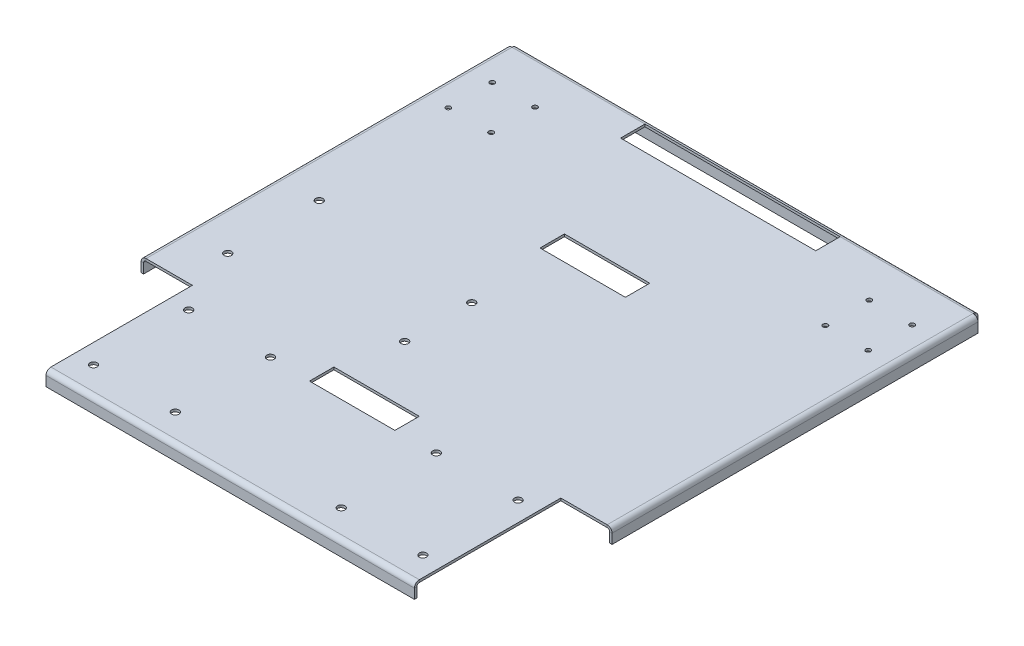
SolidWorks part; units mm, degrees
note: The reader was unsure of these and kept them because the rebuilt part matched: flange length of "Edge-Flange1", "Edge-Flange2", "Edge-Flange3", "Edge-Flange4".
ref_plane "Front Plane" through (0, 0, 0) normal (0, 0, 1) x (1, 0, 0)
ref_plane "Top Plane" through (0, 0, 0) normal (0, 1, 0) x (1, 0, 0)
ref_plane "Right Plane" through (0, 0, 0) normal (1, 0, 0) x (0, 0, -1)
sketch "Sketch1" plane through (0, 0, 0) normal (0, 1, 0) x (1, 0, 0)
  line L1 (-94.5, 104) -> (94.5, 104)
  line L2 (-94.5, 104) -> (-94.5, -104)
  line L3 (-94.5, -104) -> (94.5, -104)
  line L4 (94.5, 104) -> (94.5, -104)
  line L5 (-94.5, 104) -> (94.5, -104) construction
  line L6 (-94.5, -104) -> (94.5, 104) construction
  point P0 (0, 0)
  dimension "D1" = 208
  dimension "D2" = 189
sheet metal parameters "Sheet-Metal1" thickness 1 parameters "D1"=1
base flange "Base-Flange1" sketch "Sketch1" thickness 1 reverse thickness direction no parameters "D1"=1
edge flange "Edge-Flange1" sketch "Sketch6" flange angle 90 flange length 5 flange position bend outside bend radius 1 thickness 1 relief rectangular parameters "D6"=10
sketch "Sketch6" plane through (0, -1, 104) normal (0, 0, 1) x (-1, 0, 0)
  line L2 (-94.5, 0) -> (-94.5, 5)
  line L3 (-94.5, 5) -> (94.5, 5)
  line L4 (94.5, 5) -> (94.5, 0)
  line L5 (94.5, 0) -> (-94.5, 0) construction
  line L6 (94.5, 0) -> (-94.5, 0)
bend "EdgeBend1" bend radius 1 bend angle 90 parameters "D5"=1
edge flange "Edge-Flange2" sketch "Sketch9" flange angle 90 flange length 5 flange position bend outside bend radius 1 thickness 1 relief rectangular parameters "D6"=10
sketch "Sketch9" plane through (94.5, -1, 0) normal (1, 0, 0) x (0, 0, 1)
  line L0 (104, 0) -> (-104, 0) construction
  line L1 (104, 0) -> (-104, 0)
  line L2 (-104, 0) -> (-104, 5)
  line L3 (-104, 5) -> (104, 5)
  line L4 (104, 5) -> (104, 0)
bend "EdgeBend2" bend radius 1 bend angle 90 parameters "D5"=2
edge flange "Edge-Flange3" sketch "Sketch12" flange angle 90 flange length 5 flange position bend outside bend radius 1 thickness 1 relief rectangular parameters "D6"=10
sketch "Sketch12" plane through (0, -1, -104) normal (0, 0, -1) x (1, 0, 0)
  line L0 (94.5, 0) -> (-94.5, 0) construction
  line L1 (94.5, 0) -> (-94.5, 0)
  line L2 (-94.5, 0) -> (-94.5, 5)
  line L3 (-94.5, 5) -> (94.5, 5)
  line L4 (94.5, 5) -> (94.5, 0)
bend "EdgeBend3" bend radius 1 bend angle 90 parameters "D5"=3
edge flange "Edge-Flange4" sketch "Sketch15" flange angle 90 flange length 5 flange position bend outside bend radius 1 thickness 1 relief rectangular parameters "D6"=10
sketch "Sketch15" plane through (-94.5, -1, 0) normal (-1, 0, 0) x (0, 0, -1)
  line L0 (104, 0) -> (-104, 0) construction
  line L1 (104, 0) -> (-104, 0)
  line L2 (-104, 0) -> (-104, 5)
  line L3 (-104, 5) -> (104, 5)
  line L4 (104, 5) -> (104, 0)
bend "EdgeBend4" bend radius 1 bend angle 90 parameters "D5"=4
sketch "Sketch16" plane through (0, 0, 0) normal (0, 1, 0) x (1, 0, 0)
  line L0 (-24.2164, 108.0191) -> (-24.2164, 82.9902)
  line L1 (-24.2164, 82.9902) -> (-19.6657, 82.9902)
  line L2 (-19.6657, 82.9902) -> (-19.6657, 92.5972)
  line L3 (-19.6657, 92.5972) -> (-11.6222, 92.5972)
  line L4 (-11.6222, 92.5972) -> (-11.6222, 97.4008)
  line L5 (-11.6222, 97.4008) -> (-19.6657, 97.4008)
  line L6 (-19.6657, 97.4008) -> (-19.6657, 104.2268)
  line L7 (-19.6657, 104.2268) -> (-11.5755, 104.2268)
  line L8 (-11.5755, 104.2268) -> (-11.5755, 108.0191)
  line L9 (-11.5755, 108.0191) -> (-24.2164, 108.0191)
  line L10 (-24.2164, -84.4164) -> (-24.2164, -107.2854)
  line L11 (-24.2164, -107.2854) -> (-19.6657, -107.2854)
  line L12 (-21.752, -87.184) -> (-21.752, -92.5358)
  line L13 (-24.2164, -84.4164) -> (-19.6657, -84.4164)
  line L14 (-21.752, -92.5358) -> (-19.6657, -92.5358)
  line L15 (-21.752, -87.184) -> (-19.6657, -87.184)
  line L16 (-21.752, -98.2645) -> (-21.752, -105.2746)
  line L17 (-21.752, -98.2645) -> (-19.6657, -98.2645)
  line L18 (-21.752, -105.2746) -> (-19.6657, -105.2746)
  arc A0 (-19.6657, -84.4164) -> (-19.6657, -95.8509) centre (-19.6657, -90.1336) cw
  arc A1 (-19.6657, -95.8509) -> (-19.6657, -107.2854) centre (-19.6657, -101.5682) cw
  arc A2 (-19.6657, -87.184) -> (-19.6657, -92.5358) centre (-19.6657, -89.8599) cw
  arc A3 (-19.6657, -98.2645) -> (-19.6657, -105.2746) centre (-19.6657, -101.7695) cw
sketch "Sketch17" plane through (0, 0, 0) normal (0, 1, 0) x (1, 0, 0)
  line L0 (96.5, -104) -> (96.5, 104) construction
  line L1 (96.5, -106) -> (75.5, -106)
  line L2 (96.5, -106) -> (96.5, -46)
  line L3 (96.5, -46) -> (75.5, -46)
  line L4 (75.5, -106) -> (75.5, -46)
  line L5 (-94.5, -106) -> (94.5, -106) construction
  line L6 (0, -137.1955) -> (0, 137.1164) construction
  line L7 (-75.5, -106) -> (-75.5, -46)
  line L8 (-96.5, -46) -> (-75.5, -46)
  line L9 (-96.5, -106) -> (-96.5, -46)
  line L10 (-96.5, -106) -> (-75.5, -106)
  dimension "D1" = 0
  dimension "D2" = 60
  dimension "D3" = 21
extrude "Cut-Extrude1" cut sketch "Sketch17" against normal through all normal cut yes
sketch "Sketch18" plane through (0, 0, 0) normal (0, 1, 0) x (1, 0, 0)
  line L0 (0, -59.5649) -> (0, 146.0466) construction
  line L1 (94.5, 104) -> (-94.5, 104) construction
  line L2 (-40, 104) -> (40, 104)
  line L3 (-40, 104) -> (-40, 94)
  line L4 (-40, 94) -> (40, 94)
  line L5 (40, 104) -> (40, 94)
  line L6 (-40, 104) -> (40, 94) construction
  line L7 (-40, 94) -> (40, 104) construction
  point P3 (0, 99)
  dimension "D1" = 10
  dimension "D2" = 0
  dimension "D3" = 80
extrude "Cut-Extrude2" cut sketch "Sketch18" against normal blind 10 normal cut yes
sketch "Sketch20" plane through (0, 0, 0) normal (0, 1, 0) x (1, 0, 0)
  line L0 (-85, -46) -> (85, -46) construction
  line L1 (-75.5, -46) -> (-94.5, -46) construction
  line L2 (94.5, -46) -> (75.5, -46) construction
  line L3 (-94.5, 104) -> (-94.5, -46) construction
  line L4 (-94.5, -8.6649) -> (18.6476, -8.6649) construction
  circle A0 centre (-79.5844, -27.4149) radius 1.5
  circle A1 centre (-12.0844, -22.4149) radius 1.5
  circle A2 centre (-12.0844, 5.0851) radius 1.5
  circle A3 centre (-79.5844, 10.0851) radius 1.5
  dimension "D2" = 18.5851
  dimension "D3" = 3
  dimension "D4" = 3
  dimension "D5" = 67.5
  dimension "D6" = 5
  dimension "D1" = 14.9156
  dimension "D7" = 18.75
extrude "Cut-Extrude3" cut sketch "Sketch20" against normal blind 10 normal cut yes
sketch "Sketch21" plane through (0, 0, 0) normal (0, 1, 0) x (1, 0, 0)
  line L0 (-93.9966, 33.4732) -> (94.5, 33.4732) construction
  line L1 (94.5, -46) -> (94.5, 104) construction
  line L2 (77.2791, 93.0875) -> (77.2791, 62.1867) construction
  line L7 (63.9469, 78.4496) -> (91.7327, 78.4496) construction
  line L8 (0, 109.5327) -> (0, -141.8529) construction
  circle A0 centre (68.5, 87.4496) radius 1
  circle A1 centre (86.0583, 87.4496) radius 1
  circle A2 centre (68.5, 69.4496) radius 1
  circle A3 centre (86.0583, 69.4496) radius 1
  circle A4 centre (-86.0583, 87.4496) radius 1
  circle A5 centre (-86.0583, 69.4496) radius 1
  circle A6 centre (-68.5, 69.4496) radius 1
  circle A7 centre (-68.5, 87.4496) radius 1
  dimension "D6" = 2
extrude "Cut-Extrude4" cut sketch "Sketch21" against normal blind 10 normal cut yes
sketch "Sketch22" plane through (0, 0, 0) normal (0, 1, 0) x (1, 0, 0)
  line L0 (-75.5, -75) -> (102.8979, -75) construction
  line L1 (-75.5, -104) -> (-75.5, -46) construction
  line L2 (75.5, -46) -> (75.5, -104) construction
  line L9 (-80.5, -49) -> (80.5, -49) construction
  line L10 (-29, -51.5) -> (-29, -70) construction
  line L11 (29, -51.5) -> (29, -70) construction
  line L13 (0, -30.5194) -> (0, -140) construction
  line L14 (-80.5, -89) -> (80.5, -89) construction
  circle A0 centre (67.5, -55.5) radius 1.5
  circle A1 centre (34, -55.5) radius 1.5
  circle A2 centre (34, -94.5) radius 1.5
  circle A3 centre (67.5, -94.5) radius 1.5
  circle A4 centre (-67.5, -94.5) radius 1.5
  circle A5 centre (-34, -94.5) radius 1.5
  circle A8 centre (-34, -55.5) radius 1.5
  circle A9 centre (-67.5, -55.5) radius 1.5
  dimension "D4" = 33.5
  dimension "D1" = 8
  dimension "D2" = 8
  dimension "D3" = 33.5
extrude "Cut-Extrude5" cut sketch "Sketch22" against normal blind 10 normal cut yes
sketch "Sketch23" plane through (0, 0, 0) normal (0, 1, 0) x (1, 0, 0)
  line L0 (-93.9966, 33.4732) -> (94.5, 33.4732) construction
  line L1 (94.5, -46) -> (94.5, 104) construction
  line L2 (0, 94) -> (0, 48.4732) construction
  line L3 (-17.5, 38.4732) -> (17.5, 38.4732)
  line L4 (-17.5, 38.4732) -> (-17.5, 48.4732)
  line L5 (-17.5, 48.4732) -> (17.5, 48.4732)
  line L6 (17.5, 38.4732) -> (17.5, 48.4732)
  line L7 (-40, 94) -> (40, 94) construction
  line L8 (-92.7332, -3.7634) -> (92.74, -3.7634) construction
  line L9 (-92.7332, -38.7634) -> (-92.7332, 31.2366) construction
  line L10 (92.74, 31.2366) -> (92.74, -38.7634) construction
  line L11 (-17.5, -46) -> (-17.5, -56)
  line L12 (-17.5, -46) -> (17.5, -46)
  line L13 (17.5, -46) -> (17.5, -56)
  line L14 (-17.5, -56) -> (17.5, -56)
  dimension "D1" = 5
  dimension "D2" = 35
  dimension "D3" = 10
extrude "Cut-Extrude6" cut sketch "Sketch23" against normal blind 10 normal cut yes
flat pattern "Flat-Pattern1" [suppressed]
sketch "Bend-Lines1" plane through (0, 0, 0) normal (0, 1, 0) x (1, 0, 0)
  line L0 (-95.6781, 99) -> (-95.6781, -41) construction
  line L1 (94.5, 100.1781) -> (-94.5, 100.1781) construction
  line L2 (95.6781, -41) -> (95.6781, 99) construction
  line L3 (-75.5, -100.1781) -> (75.5, -100.1781) construction
  line L4 (-95.6781, 99) -> (-95.6781, -41) construction
  line L5 (94.5, 100.1781) -> (-94.5, 100.1781) construction
  line L6 (95.6781, -41) -> (95.6781, 99) construction
  line L7 (-75.5, -100.1781) -> (75.5, -100.1781) construction
sketch3d "Bounding-Box1" [suppressed]
  line L0 (-100.8562, 105.3562, 0) -> (-100.8562, -105.3562, 0) construction
  line L1 (100.8562, 105.3562, 0) -> (100.8562, -105.3562, 0) construction
  line L2 (-100.8562, 105.3562, 0) -> (100.8562, 105.3562, 0) construction
  line L3 (-100.8562, -105.3562, 0) -> (100.8562, -105.3562, 0) construction
bend of the flat pattern "Flatten-<EdgeBend1>1"
bend of the flat pattern "Flatten-<EdgeBend2>1"
bend of the flat pattern "Flatten-<EdgeBend3>1"
bend of the flat pattern "Flatten-<EdgeBend4>1"
sketch "Sketch24" [suppressed] plane through (0, 0, 0) normal (0, 1, 0) x (1, 0, 0)
  line L0 (94.5, 100.1781) -> (-94.5, 100.1781) construction
  line L1 (-94.5, 99) -> (-84.5, 99)
  line L2 (-94.5, 99) -> (-94.5, 101.3562)
  line L3 (-94.5, 100.1781) -> (-76.2286, 100.1781) construction
  line L4 (-84.5, 99) -> (-84.5, 101.3562)
  line L5 (-94.5, 101.3562) -> (-84.5, 101.3562)
  line L6 (0, 116.0622) -> (0, 70.299) construction
  line L7 (94.5, 101.3562) -> (84.5, 101.3562)
  line L8 (84.5, 99) -> (84.5, 101.3562)
  line L9 (94.5, 99) -> (94.5, 101.3562)
  line L10 (94.5, 99) -> (84.5, 99)
  line L11 (75.5, -41) -> (75.5, -105.3562) construction
  line L12 (75.5, -98.9992) -> (65.5, -98.9992)
  line L13 (75.5, -98.9992) -> (75.5, -101.357)
  line L14 (75.5, -100.1781) -> (60.9942, -100.1781) construction
  line L15 (65.5, -98.9992) -> (65.5, -101.357)
  line L16 (-75.5, -100.1781) -> (75.5, -100.1781) construction
  line L17 (75.5, -101.357) -> (65.5, -101.357)
  line L18 (0, -105.3562) -> (0, -85.5551) construction
  line L19 (-100.8562, -105.3562) -> (100.8562, -105.3562) construction
  line L20 (-75.5, -98.9992) -> (-75.5, -101.357)
  line L21 (-75.5, -101.357) -> (-65.5, -101.357)
  line L22 (-65.5, -98.9992) -> (-65.5, -101.357)
  line L23 (-75.5, -98.9992) -> (-65.5, -98.9992)
  point P11 (-84.5, 100.1781)
  point P18 (84.5, 100.1781)
  point P29 (65.5, -100.1781)
  dimension "D1" = 1.1781
  dimension "D2" = 10
  dimension "D3" = 1.1789
  dimension "D4" = 10
extrude "Cut-Extrude7" [suppressed] cut sketch "Sketch24" against normal blind 10
sketch "Sketch25" [suppressed] plane through (0, 0, 0) normal (0, 1, 0) x (1, 0, 0)
  line L0 (84.5, 99) -> (100.8562, 99) construction
  line L1 (94.5, 99) -> (96.8562, 99)
  line L2 (94.5, 99) -> (94.5, 89)
  line L3 (94.5, 89) -> (96.8562, 89)
  line L4 (95.6781, 99) -> (95.6781, 83.7603) construction
  line L5 (95.6781, -41) -> (95.6781, 99) construction
  line L6 (96.8562, 99) -> (96.8562, 89)
  line L7 (0, 121.3333) -> (0, -38.5667) construction
  line L8 (118.9564, 29) -> (43.7803, 29) construction
  line L9 (94.5, -31) -> (96.8562, -31)
  line L10 (96.8562, -41) -> (96.8562, -31)
  line L11 (94.5, -41) -> (96.8562, -41)
  line L12 (94.5, -41) -> (94.5, -31)
  line L13 (-94.5, -41) -> (-96.8562, -41)
  line L14 (-94.5, -31) -> (-96.8562, -31)
  line L15 (-96.8562, -41) -> (-96.8562, -31)
  line L16 (-94.5, -41) -> (-94.5, -31)
  line L17 (-94.5, 89) -> (-96.8562, 89)
  line L18 (-94.5, 99) -> (-96.8562, 99)
  line L19 (-94.5, 99) -> (-94.5, 89)
  line L20 (-96.8562, 99) -> (-96.8562, 89)
  point P11 (95.6781, 89)
  dimension "D1" = 10
  dimension "D2" = 1.1781
extrude "Cut-Extrude8" [suppressed] cut sketch "Sketch25" against normal blind 10
